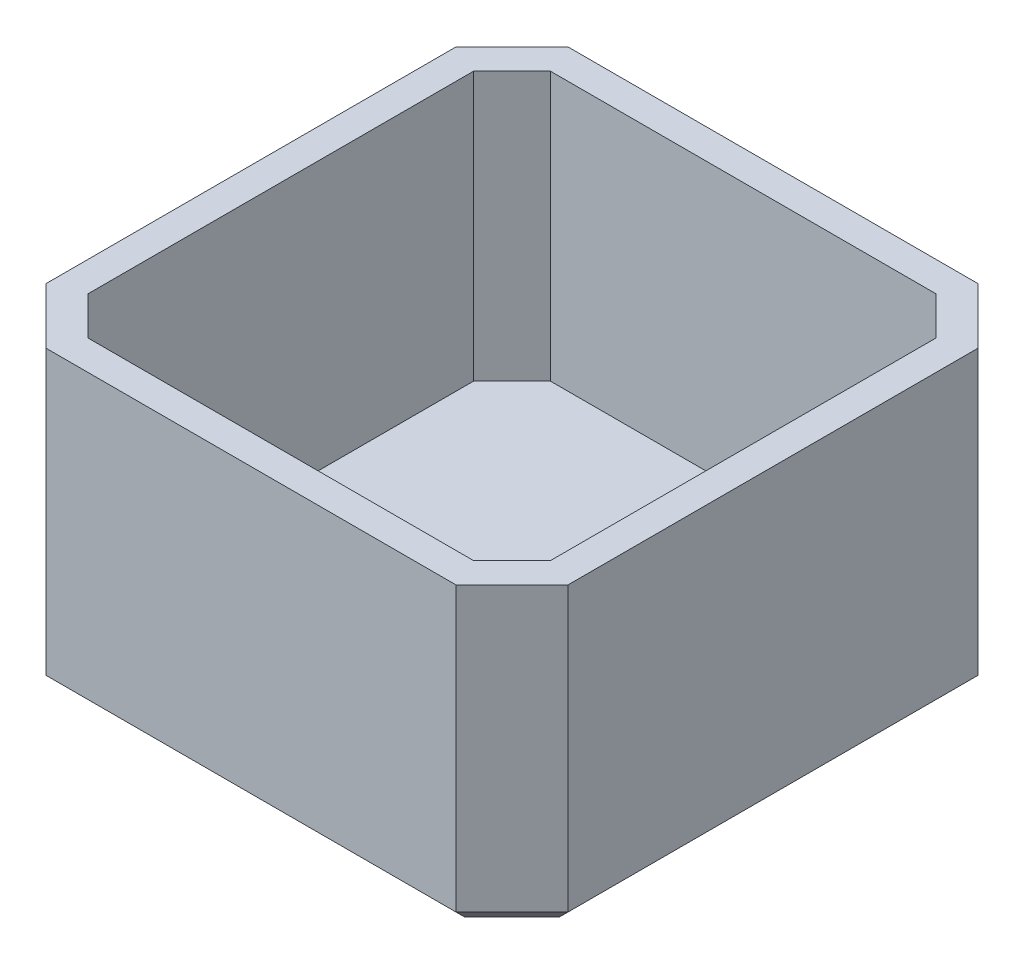
SolidWorks part; units mm, degrees
ref_plane "Alzado" through (0, 0, 0) normal (0, 0, 1) x (1, 0, 0)
ref_plane "Planta" through (0, 0, 0) normal (0, 1, 0) x (1, 0, 0)
ref_plane "Vista lateral" through (0, 0, 0) normal (1, 0, 0) x (0, 0, -1)
sketch "Croquis1" plane through (0, 0, 0) normal (0, 1, 0) x (1, 0, 0)
  line L2 (35, 27.5) -> (35, -27.5)
  line L3 (-27.5, 35) -> (27.5, 35)
  line L4 (35, 27.5) -> (27.5, 35)
  line L5 (27.5, -35) -> (-27.5, -35)
  line L6 (-27.5, -35) -> (-35, -27.5)
  line L8 (-35, 27.5) -> (-35, -27.5)
  line L9 (-35, 27.5) -> (-27.5, 35)
  line L12 (27.5, -35) -> (35, -27.5)
  point P0 (0, 0)
  point P23 (-27.8213, 34.8791)
  dimension "D1" = 55
  dimension "D2" = 70
  dimension "D3" = 27.5
  dimension "D4" = 27.5
  dimension "D6" = 70
  dimension "D7" = 55
extrude "Saliente-Extruir2" add sketch "Croquis1" along normal blind 40 contours L5 L12 L2 L4 L3 L9 L8 L6 region at (0, 0, 0)
shell "Vaciado2" thickness 4 removed face at (0, 40, 0)
chamfer "Chaflán2" distance 2 angle 45 8 edges at (-35, 0, 0) (-31.25, 0, -31.25) (0, 0, -35) (31.25, 0, -31.25) (35, 0, 0) (31.25, 0, 31.25) (0, 0, 35) (-31.25, 0, 31.25)
